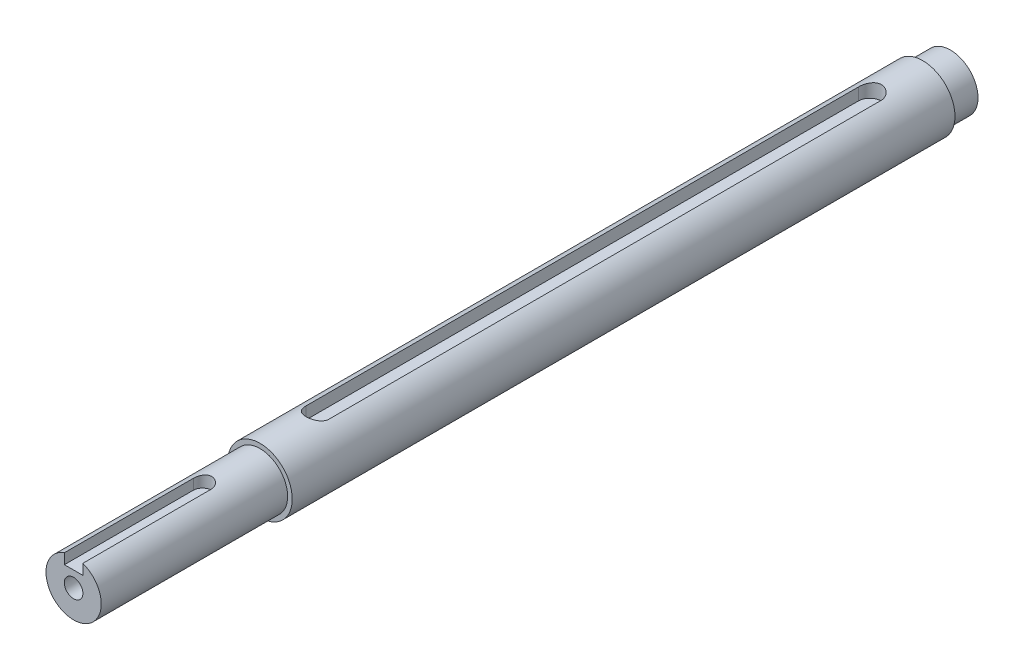
SolidWorks part; units mm, degrees
ref_plane "Front Plane" through (0, 0, 0) normal (0, 0, 1) x (1, 0, 0)
ref_plane "Top Plane" through (0, 0, 0) normal (0, 1, 0) x (1, 0, 0)
ref_plane "Right Plane" through (0, 0, 0) normal (1, 0, 0) x (0, 0, -1)
sketch "Sketch1" plane through (0, 0, 0) normal (1, 0, 0) x (0, 0, -1)
  line L0 (0, 0) -> (183, 0) construction
  line L1 (183, 0) -> (183, 6)
  line L3 (-7.5, 6) -> (-7.5, 0)
  line L5 (-7.5, 6) -> (33, 6)
  line L6 (33, 6) -> (33, 7)
  line L7 (33, 7) -> (177, 7)
  line L8 (-8, 5.9734) -> (-8, -6) construction
  line L9 (33, -12) -> (33, 12) construction
  line L10 (33, -50) -> (33, 50) construction
  line L11 (177, 7) -> (177, 6)
  line L12 (177, 6) -> (183, 6)
  line L13 (183, 0) -> (-7.5, 0)
  dimension "D1" = 12
  dimension "D2" = 0.5
  dimension "D3" = 14
  dimension "D4" = 150
  dimension "D5" = 12
  dimension "D6" = 6
revolve "Revolve1" add sketch "Sketch1" angle 360 about L0
sketch "Sketch2" plane through (0, 0, 7.5) normal (0, 0, 1) x (1, 0, 0)
  circle A0 centre (0, 0) radius 2.0193
  dimension "D1" = 4.0386
extrude "Cut-Extrude1" cut sketch "Sketch2" against normal blind 25
sketch "Sketch3" plane through (0, 0, -183) normal (0, 0, -1) x (-1, 0, 0)
  line L1 (-2.5, 8.9) -> (2.5, 8.9)
  line L2 (-2.5, 8.9) -> (-2.5, 3.9)
  line L3 (-2.5, 3.9) -> (2.5, 3.9)
  line L4 (2.5, 8.9) -> (2.5, 3.9)
  circle A1 centre (0, 0) radius 7 construction
  point P4 (0, 3.9)
  dimension "D1" = 5
  dimension "D2" = 3.1
extrude "Cut-Extrude2" cut sketch "Sketch3" against normal offset from surface (125 mm away) 10 from offset 15 contours L1 L4 L3 L2 up to face at (6, 0, -33) offset against normal yes
sketch "Sketch4" plane through (0, 0, 7.5) normal (0, 0, 1) x (1, 0, 0)
  line L1 (-2, 3.4) -> (2, 3.4)
  line L2 (-2, 3.4) -> (-2, 7.4)
  line L3 (-2, 7.4) -> (2, 7.4)
  line L4 (2, 3.4) -> (2, 7.4)
  line L5 (-2, 3.4) -> (2, 7.4) construction
  line L6 (-2, 7.4) -> (2, 3.4) construction
  circle A2 centre (0, 0) radius 6 construction
  point P0 (0, 5.4)
  point P5 (0, 0)
  dimension "D1" = 4
  dimension "D2" = 2.6
extrude "Cut-Extrude3" cut sketch "Sketch4" against normal blind 30
fillet "Fillet1" 2 edges at (-2, 4.5284, -22.5) (2, 4.5284, -22.5) type full round first side face at (-2, 4.5284, -7.5) second side face at (2, 4.5284, -7.5) middle face at (0, 4.6142, -22.5)
fillet "Fillet2" 2 edges at (-2.5, 5.2192, -43) (2.5, 5.2192, -43) type full round first side face at (-2.5, 5.2192, -105.5) second side face at (2.5, 5.2192, -105.5) middle face at (0, 5.3346, -43)
fillet "Fillet3" 2 edges at (-2.5, 5.2192, -168) (2.5, 5.2192, -168) type full round first side face at (-2.5, 5.2192, -106.75) second side face at (2.5, 5.2192, -106.75) middle face at (0, 5.3346, -168)
